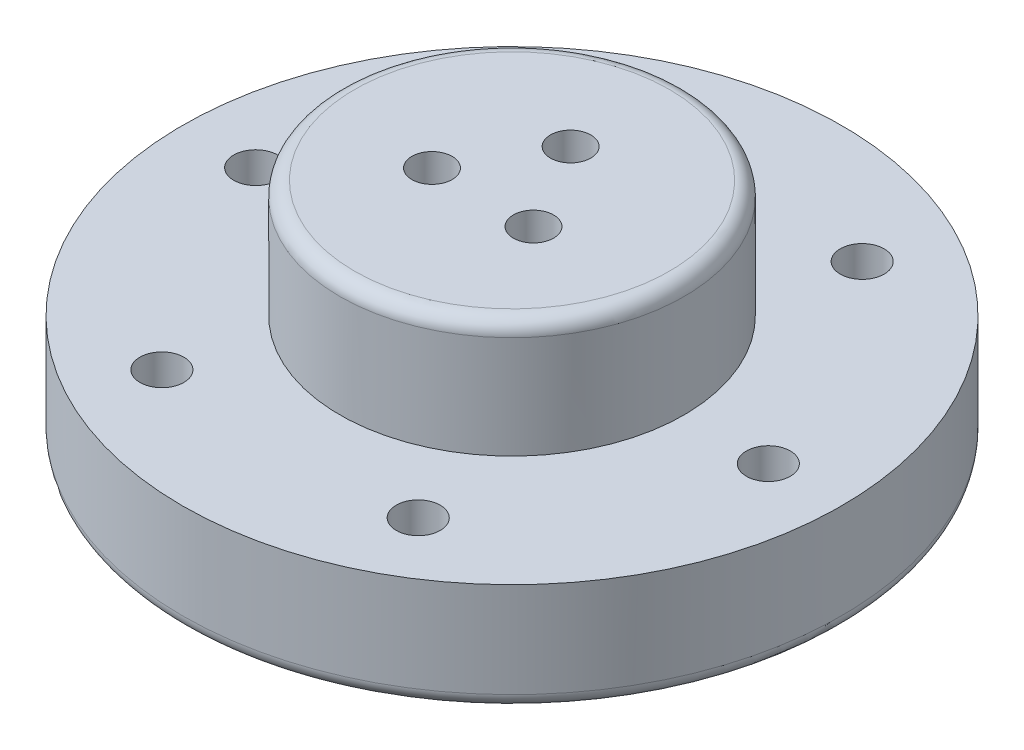
SolidWorks part; units mm, degrees
ref_plane "Front" through (0, 0, 0) normal (0, 0, 1) x (1, 0, 0)
ref_plane "Top" through (0, 0, 0) normal (0, 1, 0) x (1, 0, 0)
ref_plane "Right" through (0, 0, 0) normal (1, 0, 0) x (0, 0, -1)
sketch "Sketch1" plane through (0, 0, 0) normal (0, 1, 0) x (1, 0, 0)
  line L0 (-23.5, 0) -> (23.5, 0) construction
  line L1 (0, 25) -> (0, -42.3158) construction
  line L7 (-18.0532, -15.0443) -> (18.0532, 15.0443) construction
  line L8 (-18.0532, 15.0443) -> (18.0532, -15.0443) construction
  circle A0 centre (0, 0) radius 23.5
  dimension "D1" = 47
extrude "Boss-Extrude1" add sketch "Sketch1" along normal blind 14
sketch "Sketch2" plane through (0, 0, 0) normal (0, -1, 0) x (1, 0, 0)
  circle A0 centre (0, 0) radius 21.05
  circle A1 centre (0, 0) radius 25
  dimension "D1" = 42.1
  dimension "D2" = 50
extrude "Boss-Extrude2" add sketch "Sketch2" along normal blind 15
sketch "Sketch3" plane through (0, 0, 0) normal (0, -1, 0) x (-1, 0, 0)
  line L0 (0, 0) -> (0, 16.7758) construction
  circle A0 centre (0, 0) radius 5.65
  circle A1 centre (0, 8) radius 1.5
  circle A2 centre (6.9282, -4) radius 1.5
  circle A3 centre (-6.9282, -4) radius 1.5
  point P13 (0, 0)
  dimension "D1" = 11.3
  dimension "D2" = 8
  dimension "D3" = 3
  dimension "D4" = 3
extrude "Cut-Extrude1" cut sketch "Sketch3" against normal blind 7.5
sketch "Sketch4" plane through (0, 14, 0) normal (0, 1, 0) x (1, 0, 0)
  circle A0 centre (0, 8) radius 1.5178
  circle A2 centre (0, 0) radius 23.5
  circle A3 centre (6.9282, -4) radius 1.5
  circle A4 centre (-6.9282, -4) radius 1.5
  circle A5 centre (0, 0) radius 23.5
  dimension "D1" = 0
extrude "Boss-Extrude3" add sketch "Sketch4" along normal blind 2
ref_axis "Axis1" through (0, -15, 0) along (0, 1, 0)
sketch "Sketch5" plane through (0, 16, 0) normal (0, 1, 0) x (1, 0, 0)
  circle A0 centre (0, 8) radius 2.75
  circle A1 centre (6.9282, -4) radius 2.75
  circle A2 centre (-6.9282, -4) radius 2.75
  dimension "D1" = 5.5
  dimension "D2" = 5.5
  dimension "D3" = 5.5
extrude "Cut-Extrude2" cut sketch "Sketch5" against normal blind 6
sketch "Sketch6" plane through (0, 7.5, 0) normal (0, -1, 0) x (1, 0, 0)
  circle A0 centre (-6.9282, 4) radius 1.5 construction
  circle A1 centre (0, -8) radius 1.5 construction
  circle A2 centre (6.9282, 4) radius 1.5 construction
  circle A3 centre (-6.9282, 4) radius 1.5
  circle A4 centre (0, -8) radius 1.5
  circle A5 centre (6.9282, 4) radius 1.5
extrude "Cut-Extrude3" cut sketch "Sketch6" against normal through all
chamfer "Chamfer1" distance 1.3 angle 45 3 edges at (0, 10, -6.5) (-6.9282, 10, 5.5) (6.9282, 10, 5.5)
sketch "Sketch7" plane through (0, 0, 0) normal (0, 1, 0) x (1, 0, 0)
  line L0 (-45, 0) -> (45, 0) construction
  circle A0 centre (0, 0) radius 45
  circle A1 centre (-35, 0) radius 3
  circle A2 centre (-17.4995, 30.3118) radius 3
  circle A3 centre (17.5015, 30.3118) radius 3
  circle A4 centre (35.002, 0) radius 3
  circle A5 centre (17.5015, -30.3118) radius 3
  circle A6 centre (-17.4995, -30.3118) radius 3
  circle A7 centre (0, 0) radius 23.5
  point P8 (0, 0)
  dimension "D1" = 90
  dimension "D4" = 6
  dimension "D2" = 35
  dimension "D3" = 6
extrude "Boss-Extrude5" add sketch "Sketch7" against normal blind 15
fillet "Fillet1" radius 2 2 edges at (0, -15, 45) (0, 16, 23.5)
fillet "Fillet2" radius 1 1 edges at (0, -15, -21.05)
